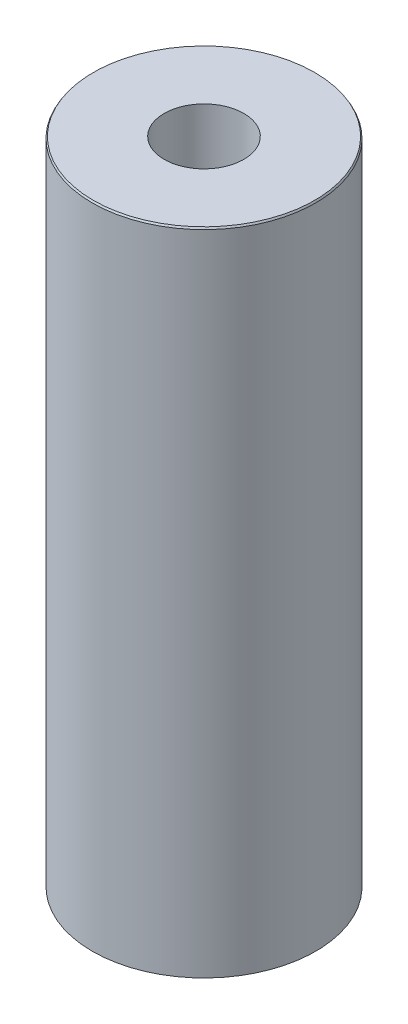
SolidWorks part; units mm, degrees
ref_plane "Front Plane" through (0, 0, 0) normal (0, 0, 1) x (1, 0, 0)
ref_plane "Top Plane" through (0, 0, 0) normal (0, 1, 0) x (1, 0, 0)
ref_plane "Right Plane" through (0, 0, 0) normal (1, 0, 0) x (0, 0, -1)
sketch "Sketch1" plane through (0, 0, 0) normal (0, 1, 0) x (1, 0, 0)
  circle A0 centre (0, 0) radius 52.5
  dimension "SHAFT_OD" = 105
extrude "Boss-Extrude1" add sketch "Sketch1" along normal blind 305.7705
sketch "Sketch2" plane through (0, 0, 0) normal (0, 1, 0) x (1, 0, 0)
  circle A0 centre (0, 0) radius 18.7174
  dimension "BORE_D" = 37.4347
extrude "Cut-Extrude1" cut sketch "Sketch2" along normal through all
chamfer "Chamfer1" distance 0.8163 angle 30 2 edges at (0, 305.7705, 52.5) (0, 0, 52.5) first distance on face at (0, 305.7705, 52.5) first distance on face at (0, 0, 18.7174)
